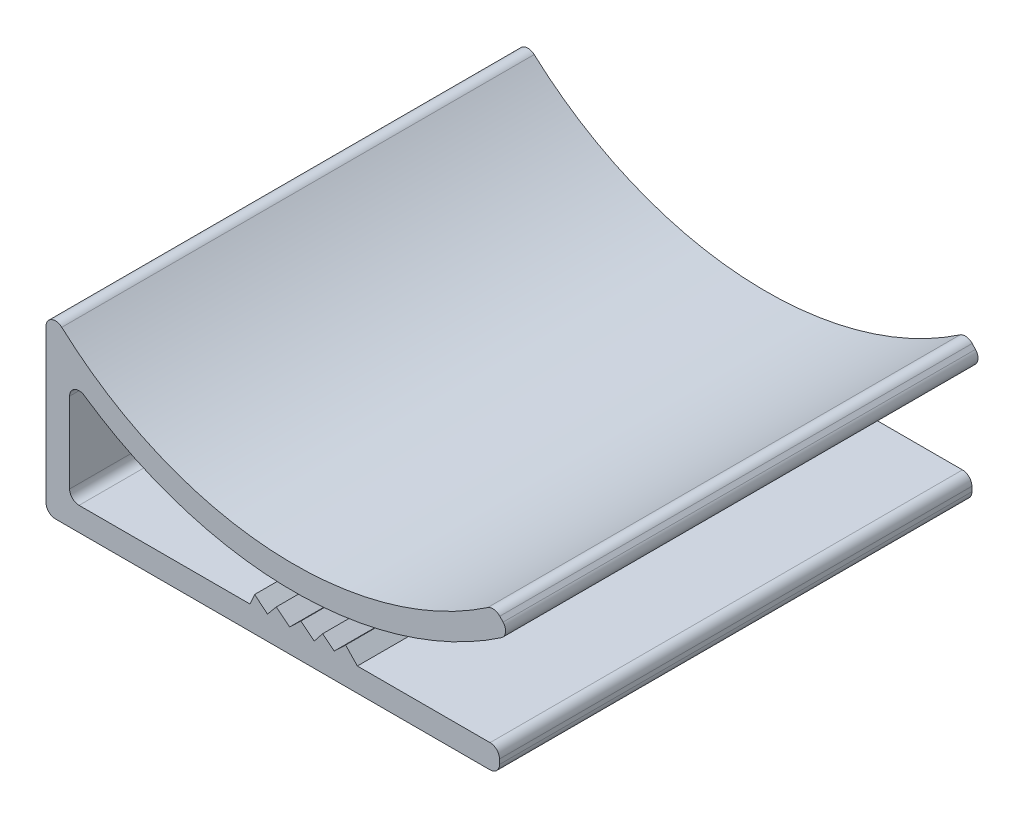
SolidWorks part; units mm, degrees
ref_plane "Alzado" through (0, 0, 0) normal (0, 0, 1) x (1, 0, 0)
ref_plane "Planta" through (0, 0, 0) normal (0, 1, 0) x (1, 0, 0)
ref_plane "Vista lateral" through (0, 0, 0) normal (1, 0, 0) x (0, 0, -1)
sketch "Croquis1" plane through (0, 0, 0) normal (0, 0, 1) x (1, 0, 0)
  line L0 (0.5, 0) -> (23.5, 0)
  line L1 (0, 0.5) -> (0, 8.5807)
  line L2 (1.75, 1.25) -> (10.798, 1.25)
  line L3 (1.25, 1.75) -> (1.25, 6.0049)
  line L4 (24, 0.5) -> (24, 0.75)
  line L6 (24.1885, 7.1165) -> (24.016, 7.3015)
  line L15 (10.798, 1.25) -> (11.0427, 1.8123)
  line L16 (11.0427, 1.8123) -> (11.7206, 1.25)
  line L17 (11.7206, 1.25) -> (12.187, 1.8123)
  line L18 (12.187, 1.8123) -> (12.8969, 1.25)
  line L19 (12.8969, 1.25) -> (13.4851, 1.8123)
  line L20 (13.4851, 1.8123) -> (14.195, 1.25)
  line L21 (14.195, 1.25) -> (14.6404, 1.8123)
  line L22 (14.6404, 1.8123) -> (15.2551, 1.3253)
  line L23 (15.2551, 1.3253) -> (15.8563, 1.9001)
  line L24 (15.8563, 1.9001) -> (16.4778, 1.25)
  line L25 (16.4778, 1.25) -> (23.5, 1.25)
  line L26 (1.25, 1.25) -> (24, 1.25) construction
  line L27 (0, 0) -> (24, 0) construction
  line L28 (1.25, 1.25) -> (1.25, 6.984) construction
  line L29 (0, 0) -> (0, 9.7555) construction
  arc A0 (0.8351, 8.9518) -> (23.3701, 7.3747) centre (13.1088, 22.5407) ccw
  arc A1 (2.0331, 6.4171) -> (10.1801, 3.1999) centre (13.1088, 22.5407) ccw
  arc A2 (10.1801, 3.1999) -> (24.1038, 6.362) centre (13.1088, 22.5407) ccw
  arc A3 (1.25, 6.984) -> (24.5688, 6.6879) centre (13.1088, 22.5407) ccw construction
  arc A4 (23.5, 0) -> (24, 0.5) centre (23.5, 0.5) ccw
  arc A5 (1.75, 1.25) -> (1.25, 1.75) centre (1.75, 1.75) cw
  arc A6 (0.5, 0) -> (0, 0.5) centre (0.5, 0.5) cw
  arc A7 (24.1038, 6.362) -> (24.1885, 7.1165) centre (23.8228, 6.7755) ccw
  arc A8 (0, 9.7555) -> (23.8365, 7.701) centre (13.1088, 22.5407) ccw construction
  arc A9 (23.3701, 7.3747) -> (24.016, 7.3015) centre (23.6503, 6.9606) cw
  arc A10 (1.25, 6.0049) -> (2.0331, 6.4171) centre (1.75, 6.0049) cw
  arc A11 (0, 8.5807) -> (0.8351, 8.9518) centre (0.5, 8.5807) cw
  arc A12 (23.5, 1.25) -> (24, 0.75) centre (23.5, 0.75) cw
  point P35 (24, 0)
  dimension "D4" = 0.5
  dimension "D1" = 0.5
  dimension "D3" = 1.25
extrude "Saliente-Extruir1" add sketch "Croquis1" along normal blind 25
ref_plane "Plane1" through (3.25, 0, 0) normal (1, 0, 0) x (0, 0, -1)
ref_plane "Plane2" through (0, 3.25, 0) normal (0, 1, 0) x (1, 0, 0)
ref_axis "Clip Axis" through (3.25, 3.25, -1.25) along (0, 0, 1)
sketch "Sketch1" plane through (0, 0, 0) normal (0, 0, -1) x (-1, 0, 0)
  point P0 (-3.25, 3.25)
sketch "Sketch2" plane through (0, 0, 25) normal (0, 0, 1) x (1, 0, 0)
  point P0 (3.25, 3.25)
ref_axis "Axis of Rotation" through (0, 9.5347, 0) along (0, -1, 0)
other "RPoint1"
other "RPoint2"
